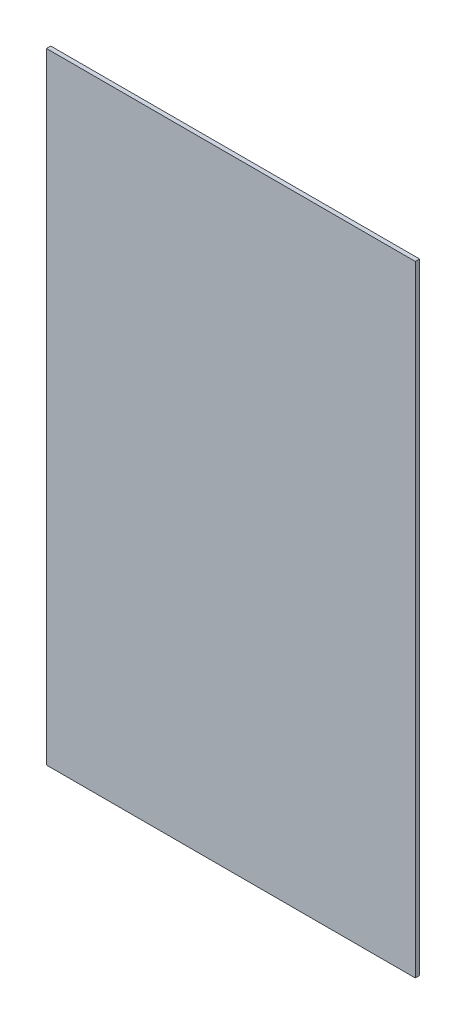
SolidWorks part; units mm, degrees
ref_plane "Спереди" through (0, 0, 0) normal (0, 0, 1) x (1, 0, 0)
ref_plane "Сверху" through (0, 0, 0) normal (0, 1, 0) x (1, 0, 0)
ref_plane "Справа" through (0, 0, 0) normal (1, 0, 0) x (0, 0, -1)
other "Configuration Table"
sketch "Эскиз1" plane through (0, 0, 0) normal (0, 0, 1) x (1, 0, 0)
  line L1 (0, -435.8) -> (-518, -435.8)
  line L2 (0, -435.8) -> (0, 435.8)
  line L3 (0, 435.8) -> (-518, 435.8)
  line L4 (-518, -435.8) -> (-518, 435.8)
extrude "Бобышка-Вытянуть1" add sketch "Эскиз1" against normal blind 6
equation "\"Ширина груза\"= 420"
equation "\"Глубина груза\"= 490"
equation "\"Высота груза\"= 297"
equation "\"Ширина ячейки\"= \"Ширина груза\" + 10"
equation "\"Глубина ячейки\"= \"Глубина груза\" + 10"
equation "\"Высота ячейки\"= \"Высота груза\" + 10 + 13"
equation "\"Колво ячеек ширина\"= 2"
equation "\"Колво ячеек высота\"= 2"
equation "\"Толщина стенки\" = 6"
equation "\"Крепление дверцы\"= 5 "
equation "\"Ширина рейки\"= \"Толщина шестерни\""
equation "\"Высота рейки\"= 20"
equation "\"Высота пола\"= \"Толщина стенки\" * 2"
equation "\"Колво полозьев\"= 5"
equation "\"Отступ рейки\"= 20"
equation "\"Глубина каретки\"= \"Глубина ячейки\" + 30 + \"Мотор Y высота корпуса\" + 20"
equation "\"Длинна рейки\"= ( \"Ширина ячейки\" + \"Толщина стенки\" + \"Крепление дверцы\" ) * \"Колво ячеек ширина\" + \"Ширина ячейки выгрузки\" * \"Колво выгрузки\" + \"Толщина стенки\""
equation "\"Отступ шпильки\"= 26"
equation "\"Диаметр шпильки\"= 5"
equation "\"Длинна шпильки\"= ( \"Высота ячейки\" + \"Толщина стенки\" + \"Высота пола\" ) * \"Колво ячеек высота\" + ( \"Толщина стенки\" + \"Отступ рейки\" ) * 2 "
equation "\"Ширина пластины\"= 50  "
equation "\"Высота зона выгрузки\"= \"Высота ячейки\" * 2 + \"Толщина стенки\" * 2"
equation "\"Колво выгрузки\"= 1"
equation "\"Ширина ячейки выгрузки\"= \"Ширина ячейки\" + \"Толщина стенки\" + \"Отступ крепления мотора фиксации\"*2"
equation "\"Отступ крепления мотора фиксации\" = 30"
equation "\"Мотор X ширина корпуса\"= 42.3"
equation "\"Мотор X высота корпуса\"= 42.3"
equation "\"Мотор X длина корпуса\"= 40"
equation "\"Мотор X вылет вала\"= 19.8"
equation "\"Мотор Y ширина корпуса\"= 42.3"
equation "\"Мотор Y высота корпуса\"= 42.3"
equation "\"Мотор Y длина корпуса\"= 48"
equation "\"Мотор Y вылет вала\"= 30"
equation "\"Мотор Z ширина корпуса\"= 42"
equation "\"Мотор Z высота корпуса\"= 42"
equation "\"Мотор Z длина корпуса\"= 40"
equation "\"Мотор Z вылет вала\"= 23"
equation "\"Мотор диаметр вала ПРЕДВ\"= 5"
equation "\"Мотор шаг крепления ПРЕДВ\"= 31"
equation "\"Мотор диаметр отверстий ПРЕДВ\"= 3"
equation "\"Мотор глубина отверстий ПРЕДВ\"= 4.5"
equation "\"Мотор диаметр буртика ПРЕДВ\"= 22"
equation "\"Мотор высота буртика ПРЕДВ\"= 2"
equation "\"Мотор диаметр шкива ПРЕДВ\"= 16"
equation "\"Мотор длина шкива ПРЕДВ\"= 12"
equation "\"Мотор отступ шкива ПРЕДВ\"= 5"
equation "\"Мотор X шаг градусов\"= 1.8"
equation "\"Мотор Y шаг градусов\"= 1.8"
equation "\"Мотор Z шаг градусов\"= 1.8"
equation "\"Мотор Y диаметр ротора\"= 25.78"
equation "\"Толщина шестерни\"= 10"
equation "\"D1@Бобышка-Вытянуть1\"=\"Толщина стенки\""
